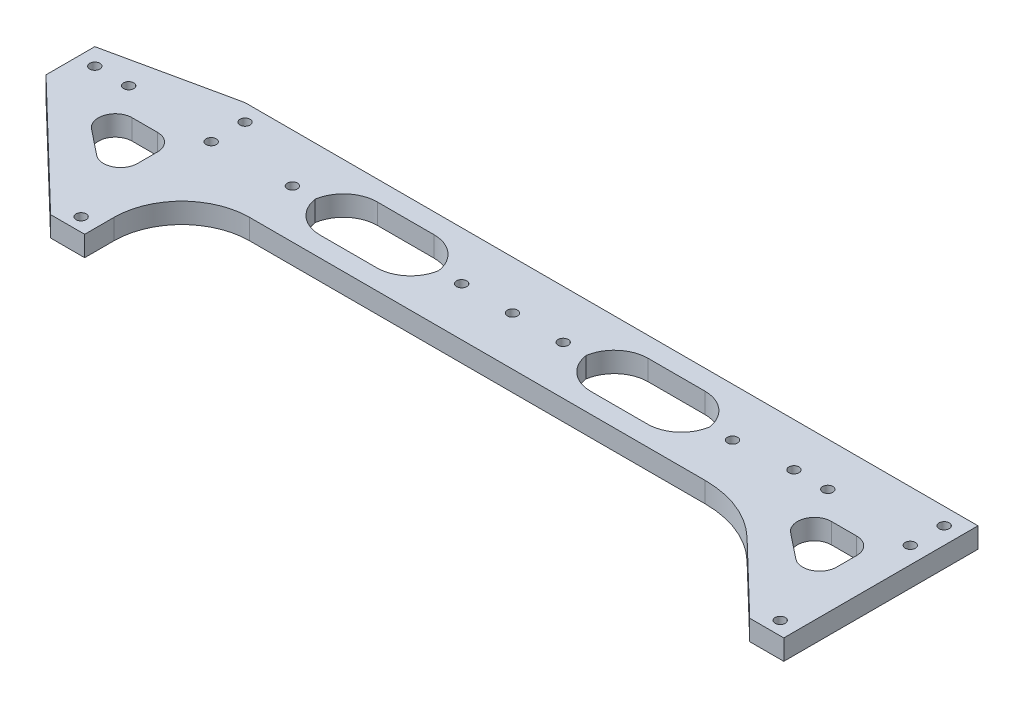
SolidWorks part; units mm, degrees
ref_plane "Front Plane" through (0, 0, 0) normal (0, 0, 1) x (1, 0, 0)
ref_plane "Top Plane" through (0, 0, 0) normal (0, 1, 0) x (1, 0, 0)
ref_plane "Right Plane" through (0, 0, 0) normal (1, 0, 0) x (0, 0, -1)
sketch "Sketch1" plane through (0, 0, 0) normal (0, 1, 0) x (1, 0, 0)
  line L0 (0, 0) -> (0, 10.18) construction
  line L1 (0, 10.18) -> (36.5, 10.18) construction
  line L2 (0, 0) -> (0, 51.73) construction
  line L3 (36.5, 10.18) -> (36.5, 49.6) construction
  line L4 (36.5, 49.6) -> (36.5, 59.6) construction
  line L5 (0, 0) -> (0, -5) construction
  line L7 (0, 51.73) -> (0, 56.73) construction
  line L8 (5, 56.73) -> (-5, 56.73)
  line L9 (-5, 56.73) -> (-5, -5)
  line L10 (5, 56.73) -> (5, 16.6667)
  line L11 (36.5, 59.6) -> (36.5, 64.6) construction
  line L12 (41.5, 64.6) -> (31.5, 64.6)
  line L13 (36.5, 10.18) -> (36.5, -19.82) construction
  line L15 (31.5, 64.6) -> (31.5, 16.6667)
  line L16 (41.5, 64.6) -> (41.5, -19.82)
  line L17 (31.5, 64.6) -> (-5, 56.73)
  line L18 (5, 56.73) -> (31.5, 54.48)
  line L19 (5, 16.6667) -> (31.5, 16.6667)
  line L20 (5, 5.234) -> (31.5, 5.234)
  line L21 (5, 5.234) -> (5, -5)
  line L22 (5, 5.234) -> (-5, 5.234)
  line L23 (-5, 5.234) -> (41.5, 5.234)
  line L24 (31.5, 5.234) -> (31.5, -19.82)
  line L25 (36.5, 10.18) -> (39.514, 10.18) construction
  line L26 (39.514, 10.18) -> (39.514, 11.18) construction
  line L27 (39.514, 11.18) -> (36.5, 11.18) construction
  circle A2 centre (0, 51.73) radius 1.5
  circle A3 centre (36.5, 49.6) radius 1.5
  circle A4 centre (36.5, 59.6) radius 1.5
  circle A5 centre (0, 10.18) radius 1.5
  circle A6 centre (36.5, 11.18) radius 1.5
  dimension "D1" = 10.18
  dimension "D2" = 36.5
  dimension "D3" = 51.73
  dimension "D4" = 39.42
  dimension "D5" = 10
  dimension "D6" = 5
  dimension "D12" = 1
  dimension "D7" = 5
  dimension "D8" = 5
  dimension "D9" = 5
  dimension "D10" = 5
  dimension "D11" = 5
extrude "Boss-Extrude1" add sketch "Sketch1" along normal blind 3 contours L16 L12 L15 A4 A3 | L8 L18 L15 L17 | L10 L8 L9 A2 A5 | L10 L15 region at (4.2459, 0, -36.6984) region at (18.1224, 0, -36.1413) region at (19.9063, 0, -58.7735)
sketch "Sketch4" plane through (0, 3, 0) normal (0, 1, 0) x (1, 0, 0)
  line L0 (0, 51.73) -> (10, 51.73) construction
  circle A0 centre (10, 51.73) radius 1.5
extrude "Cut-Extrude2" cut sketch "Sketch4" against normal blind 7
sketch "Sketch5" plane through (0, 3, 0) normal (0, 1, 0) x (1, 0, 0)
  line L0 (-5, 5.234) -> (-5, 7.234) construction
  line L1 (-5, 56.73) -> (-5, 5.234) construction
  line L3 (-5, 7.234) -> (41.5, 7.234)
  line L4 (-5, 7.234) -> (-5, 5.234)
  line L5 (-5, 5.234) -> (41.5, 5.234)
  line L6 (41.5, 7.234) -> (41.5, 5.234)
  dimension "D1" = 2
extrude "Cut-Extrude3" cut sketch "Sketch5" against normal blind 7
sketch "Sketch6" plane through (0, 3, 0) normal (0, 1, 0) x (1, 0, 0)
  line L0 (31.4436, 7.234) -> (-5, 42.3128)
  line L1 (41.5, 7.234) -> (-5, 7.234) construction
  line L2 (-5, 56.73) -> (-5, 7.234) construction
  line L3 (-5, 42.3128) -> (-5, 7.234)
  line L4 (-5, 7.234) -> (31.4436, 7.234)
extrude "Cut-Extrude4" cut sketch "Sketch6" against normal blind 7
sketch "Sketch7" plane through (0, 3, 0) normal (0, 1, 0) x (1, 0, 0)
  line L0 (31.1931, 22.7729) -> (31.1931, 44.0664)
  line L1 (31.1931, 44.0664) -> (4.3883, 44.0664)
  line L2 (4.3883, 44.0664) -> (31.1931, 22.7729)
extrude "Cut-Extrude5" cut sketch "Sketch7" against normal blind 7
sketch "Sketch8" plane through (0, 3, 0) normal (0, 1, 0) x (1, 0, 0)
  line L0 (41.5, 64.6) -> (31.5, 64.6)
  line L1 (31.5, 64.6) -> (-5, 56.73)
  line L2 (31.5, 64.6) -> (-5, 56.73) construction
  line L3 (-5, 56.73) -> (-5, 42.3128)
  line L4 (-5, 42.3128) -> (31.4436, 7.234)
  line L5 (31.4436, 7.234) -> (41.5, 7.234)
  line L6 (41.5, 64.6) -> (41.5, 7.234) construction
  line L7 (41.5, 7.234) -> (41.5, 64.6)
  line L8 (4.3883, 44.0664) -> (31.1931, 44.0664)
  line L9 (31.1931, 44.0664) -> (31.1931, 22.7729)
  line L10 (31.1931, 22.7729) -> (4.3883, 44.0664)
  line L11 (41.5, 35.917) -> (201.5, 35.917) construction
  line L12 (201.5, 35.917) -> (201.5, 86.7417) construction
  line L13 (248, 64.6) -> (238, 64.6)
  line L14 (238, 64.6) -> (201.5, 56.73)
  line L15 (201.5, 56.73) -> (201.5, 42.3128)
  line L16 (201.5, 42.3128) -> (237.9436, 7.234)
  line L17 (237.9436, 7.234) -> (248, 7.234)
  line L18 (248, 7.234) -> (248, 64.6)
  line L19 (210.8883, 44.0664) -> (237.6931, 44.0664)
  line L20 (237.6931, 44.0664) -> (237.6931, 22.7729)
  line L21 (237.6931, 22.7729) -> (210.8883, 44.0664)
  line L22 (41.5, 64.6) -> (248, 64.6)
  line L23 (41.5, 35.917) -> (208.1446, 35.917)
  circle A0 centre (0, 51.73) radius 1.5
  circle A1 centre (10, 51.73) radius 1.5
  circle A2 centre (36.5, 49.6) radius 1.5
  circle A3 centre (36.5, 59.6) radius 1.5
  circle A4 centre (36.5, 11.18) radius 1.5
  circle A5 centre (206.5, 51.73) radius 1.5
  circle A6 centre (216.5, 51.73) radius 1.5
  circle A7 centre (243, 49.6) radius 1.5
  circle A8 centre (243, 59.6) radius 1.5
  circle A9 centre (243, 11.18) radius 1.5
  line M30 (31.1931, 22.7729) -> (4.3883, 44.0664)
  line M31 (4.3883, 44.0664) -> (31.1931, 44.0664)
  line M32 (31.1931, 44.0664) -> (31.1931, 22.7729)
  line M33 (-5, 42.3128) -> (31.4436, 7.234)
  line M34 (31.4436, 7.234) -> (41.5, 7.234)
  line M35 (41.5, 7.234) -> (41.5, 64.6)
  line M36 (41.5, 64.6) -> (31.5, 64.6)
  line M37 (31.5, 64.6) -> (-5, 56.73)
  line M38 (-5, 56.73) -> (-5, 42.3128)
  circle M39 centre (10, 51.73) radius 1.5
  circle M40 centre (36.5, 11.18) radius 1.5
  circle M41 centre (36.5, 59.6) radius 1.5
  circle M42 centre (36.5, 49.6) radius 1.5
  circle M43 centre (0, 51.73) radius 1.5
  dimension "D1" = 160
  dimension "D2" = 2
extrude "Boss-Extrude2" add sketch "Sketch8" against normal blind 6 contours L7 L23 L16 L15 L14 L22 | L17 L18 L13 L14 L15 L16 A9 A8 A7 A6 A5 L20 L21 L19 | L7 M38 M33 M34 M35 M36 M37 M39 M41 M43 M42 M40 M32 M30 M31 region at (40.7615, 3, -50.2585) region at (124.6519, 3, -50.558) region at (243, 3, -63.8615)
sketch "Sketch9" plane through (0, 3, 0) normal (0, 1, 0) x (1, 0, 0)
  line L0 (124.8223, 35.917) -> (124.8223, 64.6) construction
  line L1 (41.5, 35.917) -> (208.1446, 35.917) construction
  line L2 (248, 64.6) -> (31.5, 64.6) construction
  line L3 (124.8223, 50.2585) -> (59.8223, 50.2585) construction
  circle A0 centre (59.8223, 50.2585) radius 1.5
  circle A1 centre (189.8223, 50.2585) radius 1.5
  circle A2 centre (124.8223, 50.2585) radius 1.5
  dimension "D1" = 65
extrude "Cut-Extrude6" cut sketch "Sketch9" against normal blind 6
sketch "Sketch10" plane through (0, 3, 0) normal (0, 1, 0) x (1, 0, 0)
  line L0 (124.8223, 50.2585) -> (109.8223, 50.2585) construction
  line L1 (124.8223, 50.2585) -> (139.8223, 50.2585) construction
  circle A0 centre (124.8223, 50.2585) radius 1.5
  circle A1 centre (109.8223, 50.2585) radius 1.5
  circle A2 centre (139.8223, 50.2585) radius 1.5
  dimension "D2" = 15
  dimension "D1" = 15
extrude "Cut-Extrude7" cut sketch "Sketch10" against normal blind 6
sketch "Sketch11" plane through (0, 3, 0) normal (0, 1, 0) x (1, 0, 0)
  line L0 (59.8223, 50.2585) -> (109.8223, 50.2585) construction
  line L1 (124.8223, 50.2585) -> (124.8223, 64.6) construction
  line L2 (66.4377, 41.7958) -> (103.2069, 41.7958)
  line L3 (66.4377, 41.7958) -> (66.4377, 58.7212)
  line L4 (66.4377, 58.7212) -> (103.2069, 58.7212)
  line L5 (103.2069, 41.7958) -> (103.2069, 58.7212)
  line L6 (66.4377, 41.7958) -> (103.2069, 58.7212) construction
  line L7 (66.4377, 58.7212) -> (103.2069, 41.7958) construction
  line L8 (248, 64.6) -> (31.5, 64.6) construction
  line L9 (183.2069, 58.7212) -> (146.4377, 58.7212)
  line L10 (146.4377, 41.7958) -> (146.4377, 58.7212)
  line L11 (183.2069, 41.7958) -> (146.4377, 41.7958)
  line L12 (183.2069, 41.7958) -> (183.2069, 58.7212)
  point P4 (84.8223, 50.2585)
extrude "Cut-Extrude8" cut sketch "Sketch11" against normal blind 14 contours L3 L2 L5 L4 | L9 L10 L11 L12
fillet "Fillet2" radius 5 6 edges at (31.1931, 0, -44.0664) (4.3883, 0, -44.0664) (31.1931, 0, -22.7729) (237.6931, 0, -22.7729) (210.8883, 0, -44.0664) (237.6931, 0, -44.0664)
fillet "Fillet3" radius 10 8 edges at (183.2069, 0, -41.7958) (183.2069, 0, -58.7212) (146.4377, 0, -41.7958) (146.4377, 0, -58.7212) (103.2069, 0, -41.7958) (66.4377, 0, -41.7958) (66.4377, 0, -58.7212) (103.2069, 0, -58.7212)
fillet "Fillet4" radius 20 1 edges at (41.5, 0, -35.917)
fillet "Fillet5" radius 30 1 edges at (208.1446, 0, -35.917)
fillet "Fillet6" radius 10 1 edges at (31.5, 0, -64.6)
